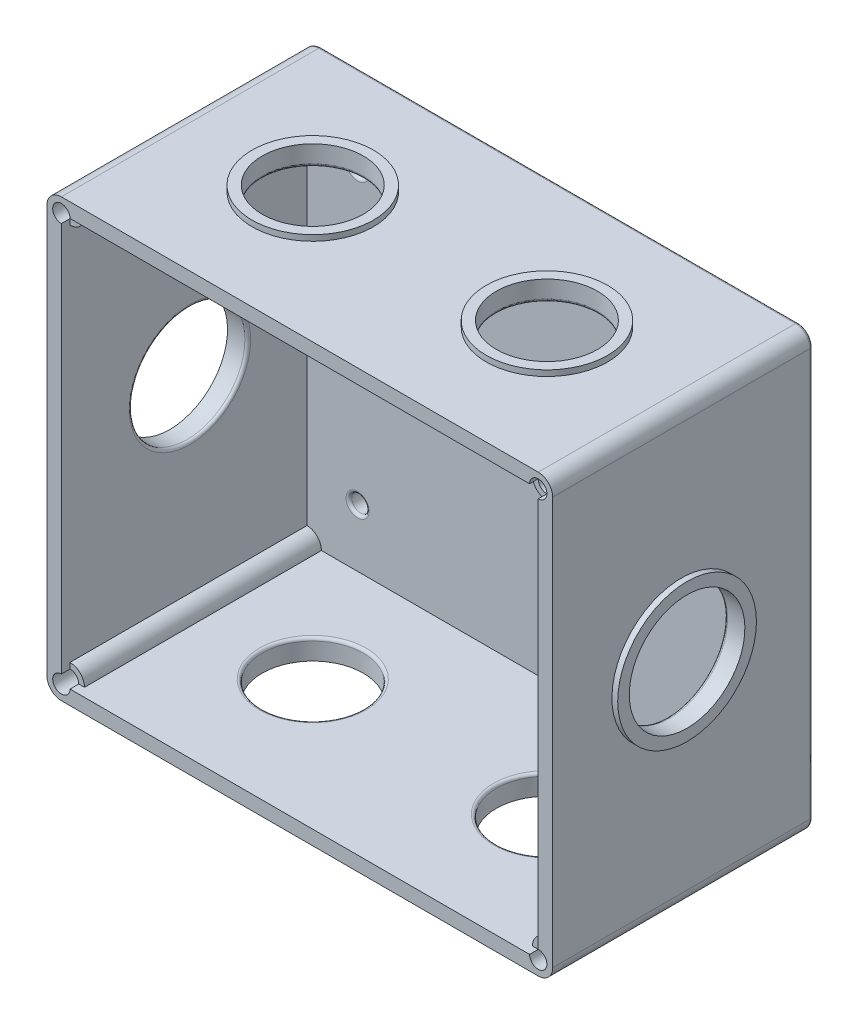
SolidWorks part; units mm, degrees
material "ABS"
ref_plane "Plan de face" through (0, 0, 0) normal (0, 0, 1) x (1, 0, 0)
ref_plane "Plan de dessus" through (0, 0, 0) normal (0, 1, 0) x (1, 0, 0)
ref_plane "Plan de droite" through (0, 0, 0) normal (1, 0, 0) x (0, 0, -1)
sketch "Esquisse1" plane through (0, 0, 0) normal (0, 0, 1) x (1, 0, 0)
  line L1 (5, 0) -> (170, 0)
  line L2 (0, 5) -> (0, 146)
  line L3 (5, 151) -> (170, 151)
  line L4 (175, 5) -> (175, 146)
  arc A0 (175, 5) -> (170, 0) centre (170, 5) cw
  arc A1 (5, 0) -> (0, 5) centre (5, 5) cw
  arc A2 (0, 146) -> (5, 151) centre (5, 146) cw
  arc A3 (170, 151) -> (175, 146) centre (170, 146) cw
  point P7 (175, 0)
  point P10 (0, 0)
  point P13 (0, 151)
  point P16 (175, 151)
  dimension "D3" = 5
  dimension "D1" = 175
  dimension "D2" = 151
extrude "Boss.-Extru.1" add sketch "Esquisse1" along normal blind 90
shell "Coque1" thickness 5 removed face at (87.5, 75.5, 90)
sketch "Esquisse2" plane through (0, 0, 5) normal (0, 0, 1) x (1, 0, 0)
  line L0 (5, 146) -> (170, 146) construction
  line L1 (170, 146) -> (170, 5) construction
  line L2 (170, 5) -> (5, 5) construction
  line L3 (5, 5) -> (5, 146) construction
  line L4 (5, 146) -> (87.5, 146) construction
  line L5 (87.5, 146) -> (87.5, 5) construction
  line L6 (87.5, 5) -> (87.5, 75.5) construction
  line L7 (87.5, 75.5) -> (170, 75.5) construction
  line L8 (170, 75.5) -> (5, 75.5) construction
  line L9 (5, 146) -> (9.9922, 146) construction
  line L10 (9.9922, 146) -> (9.9922, 141.0078) construction
  line L11 (9.9922, 141.0078) -> (5, 141.0078) construction
  line L12 (5, 141.0078) -> (5, 146)
  line L13 (5, 146) -> (9.9922, 146)
  line L14 (170, 146) -> (165.0078, 146)
  line L15 (170, 141.0078) -> (170, 146)
  line L16 (170, 5) -> (165.0078, 5)
  line L17 (170, 9.9922) -> (170, 5)
  line L18 (5, 9.9922) -> (5, 5)
  line L19 (5, 5) -> (9.9922, 5)
  arc A0 (9.9922, 146) -> (5, 141.0078) centre (5, 146) cw
  arc A1 (165.0078, 146) -> (170, 141.0078) centre (170, 146) ccw
  arc A2 (165.0078, 5) -> (170, 9.9922) centre (170, 5) cw
  arc A3 (9.9922, 5) -> (5, 9.9922) centre (5, 5) ccw
  point P17 (5, 145.9998)
  point P18 (0, 0)
  point P19 (5, 141.0028)
extrude "Boss.-Extru.2" add sketch "Esquisse2" along normal blind 82
sketch "Esquisse3" plane through (0, 0, 90) normal (0, 0, 1) x (1, 0, 0)
  line L0 (87.5, 146) -> (87.5, 5) construction
  line L1 (165.0078, 146) -> (9.9922, 146) construction
  line L2 (5, 5) -> (170, 5) construction
  line L3 (87.5, 5) -> (87.5, 75.5) construction
  line L4 (87.5, 75.5) -> (5, 75.5) construction
  line L5 (5, 146) -> (5, 5) construction
  circle A0 centre (5, 146) radius 3
  circle A1 centre (170, 146) radius 3
  circle A2 centre (170, 5) radius 3
  circle A3 centre (5, 5) radius 3
extrude "Enlèv. mat.-Extru.1" cut sketch "Esquisse3" against normal blind 18
sketch "Esquisse4" plane through (0, 0, 5) normal (0, 0, 1) x (1, 0, 0)
  line L0 (166.4699, 142.4699) -> (8.5301, 8.5301) construction
  line L1 (8.5301, 142.4699) -> (166.4699, 8.5301) construction
  line L2 (87.5, 75.5) -> (87.5, 125.9905) construction
  line L3 (87.5, 125.9905) -> (22.5048, 125.9905) construction
  line L4 (87.5, 75.5) -> (170, 75.5) construction
  line L5 (170, 9.9922) -> (170, 141.0078) construction
  arc A0 (165.0078, 146) -> (170, 141.0078) centre (170, 146) ccw construction
  arc A1 (9.9922, 5) -> (5, 9.9922) centre (5, 5) ccw construction
  arc A2 (5, 141.0078) -> (9.9922, 146) centre (5, 146) ccw construction
  arc A3 (170, 9.9922) -> (165.0078, 5) centre (170, 5) ccw construction
  circle A4 centre (22.5048, 125.9905) radius 3
  circle A5 centre (152.4952, 125.9905) radius 3
  circle A6 centre (152.4952, 25.0095) radius 3
  circle A7 centre (22.5048, 25.0095) radius 3
  circle A8 centre (128.75, 75.5) radius 3
  circle A9 centre (46.25, 75.5) radius 3
extrude "Enlèv. mat.-Extru.2" cut sketch "Esquisse4" against normal blind 5
sketch "Esquisse5" plane through (0, 151, 0) normal (0, 1, 0) x (1, 0, 0)
  line L0 (5, 0) -> (87.5, 0) construction
  line L1 (170, 0) -> (5, 0) construction
  line L2 (87.5, 0) -> (87.5, -90) construction
  line L3 (170, -90) -> (5, -90) construction
  line L4 (87.5, -90) -> (87.5, -45) construction
  line L5 (87.5, -45) -> (170, -45) construction
  line L6 (170, -90) -> (170, 0) construction
  circle A0 centre (128.0183, -45) radius 17.5
  circle A1 centre (46.9817, -45) radius 17.5
  dimension "D1" = 35
extrude "Enlèv. mat.-Extru.3" cut sketch "Esquisse5" against normal blind 165
sketch "Esquisse7" plane through (0, 151, 0) normal (0, 1, 0) x (1, 0, 0)
  line L0 (87.5, 0) -> (87.5, -90) construction
  line L1 (170, 0) -> (5, 0) construction
  line L2 (170, -90) -> (5, -90) construction
  circle A0 centre (128.0183, -45) radius 21
  circle A1 centre (46.9817, -45) radius 21
  circle A2 centre (46.9817, -45) radius 17.5
  circle A3 centre (128.0183, -45) radius 17.5
extrude "Boss.-Extru.3" add sketch "Esquisse7" along normal blind 2
sketch "Esquisse8" plane through (0, 0, 0) normal (0, -1, 0) x (1, 0, 0)
  circle A0 centre (46.9817, 45) radius 17.5
  circle A1 centre (46.9817, 45) radius 21
  circle A2 centre (128.0183, 45) radius 17.5
  circle A3 centre (128.0183, 45) radius 21
extrude "Boss.-Extru.4" add sketch "Esquisse8" along normal blind 2
fillet "Congé1" radius 1 4 edges at (128.0183, 5, 62.5) (46.9817, 5, 62.5) (128.0183, 146, 27.5) (46.9817, 146, 27.5)
fillet "Congé2" radius 1 4 edges at (19.5048, 25.0095, 5) (155.4952, 25.0095, 5) (149.4952, 125.9905, 5) (25.5048, 125.9905, 5)
fillet "Congé3" radius 1 8 edges at (173.5355, 149.5355, 0) (175, 75.5, 0) (173.5355, 1.4645, 0) (87.5, 0, 0) (1.4645, 1.4645, 0) (0, 75.5, 0) (1.4645, 149.5355, 0) (87.5, 151, 0)
sketch "Esquisse9" plane through (0, 0, 0) normal (-1, 0, 0) x (0, 0, 1)
  line L0 (1, 146) -> (1, 5) construction
  line L1 (1, 5) -> (90, 5) construction
  line L2 (90, 5) -> (1, 146) construction
  line L3 (1, 146) -> (90, 146) construction
  line L4 (90, 146) -> (1, 5) construction
  line L5 (1, 75.5) -> (90, 75.5) construction
  line L6 (90, 146) -> (90, 5) construction
  line L7 (90, 75.5) -> (45.5, 146) construction
  line L8 (45.5, 146) -> (45.5, 5) construction
  circle A0 centre (45.5, 75.5) radius 20
extrude "Enlèv. mat.-Extru.4" cut sketch "Esquisse9" against normal blind 192
fillet "Congé4" radius 1 2 edges at (170, 55.5, 45.5) (5, 95.5, 45.5)
sketch "Esquisse10" plane through (0, 0, 0) normal (-1, 0, 0) x (0, 0, 1)
  circle A0 centre (45.5, 75.5) radius 20
  circle A1 centre (45.5, 75.5) radius 24
extrude "Boss.-Extru.5" add sketch "Esquisse10" along normal blind 2
sketch "Esquisse11" plane through (175, 0, 0) normal (1, 0, 0) x (0, 0, -1)
  circle A0 centre (-45.5, 75.5) radius 20
  circle A1 centre (-45.5, 75.5) radius 24
extrude "Boss.-Extru.6" add sketch "Esquisse11" along normal blind 2
sketch "Esquisse12" plane through (0, 0, 90) normal (0, 0, 1) x (1, 0, 0)
  line L0 (5, 146) -> (170, 146) construction
  line L1 (170, 146) -> (170, 5) construction
